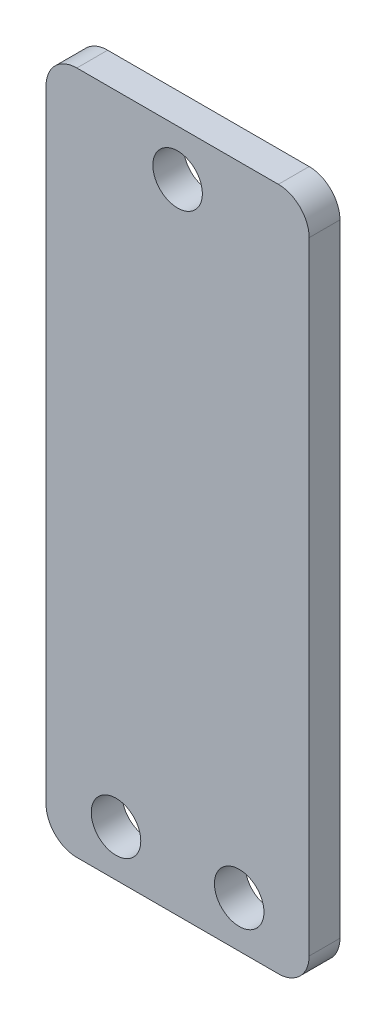
SolidWorks part; units mm, degrees
ref_plane "Front Plane" through (0, 0, 0) normal (0, 0, 1) x (1, 0, 0)
ref_plane "Top Plane" through (0, 0, 0) normal (0, 1, 0) x (1, 0, 0)
ref_plane "Right Plane" through (0, 0, 0) normal (1, 0, 0) x (0, 0, -1)
sketch "Sketch1" plane through (0, 0, 0) normal (0, 0, 1) x (1, 0, 0)
  line L0 (8.9027, -4.6609) -> (-8.9027, -4.6609) construction
  line L1 (10.3886, -4.6609) -> (-10.3886, -4.6609)
  line L2 (13.5636, -1.4859) -> (13.5636, 62.6618)
  line L3 (10.3886, 65.8368) -> (-10.3886, 65.8368)
  line L4 (-13.5636, -1.4859) -> (-13.5636, 62.6618)
  line L5 (70.917, 65.8368) -> (26.467, 65.8368) construction
  arc A0 (8.9027, -4.6609) -> (8.9027, 4.6609) centre (8.9027, 0) ccw construction
  arc A1 (-8.9027, 4.6609) -> (-8.9027, -4.6609) centre (-8.9027, 0) ccw construction
  arc A2 (13.5636, 62.6618) -> (10.3886, 65.8368) centre (10.3886, 62.6618) ccw
  arc A3 (-10.3886, 65.8368) -> (-13.5636, 62.6618) centre (-10.3886, 62.6618) ccw
  arc A4 (-10.3886, -4.6609) -> (-13.5636, -1.4859) centre (-10.3886, -1.4859) cw
  arc A5 (10.3886, -4.6609) -> (13.5636, -1.4859) centre (10.3886, -1.4859) ccw
  dimension "D1" = 3.175
extrude "Boss-Extrude1" add sketch "Sketch1" along normal blind 3.175
hole_wizard "#10 Clearance Hole1" positions "Sketch2" profile "Sketch3" hole size "#10" standard "ANSI Inch" end condition through all
sketch "Sketch2" plane through (0, 0, 3.175) normal (0, 0, 1) x (1, 0, 0)
  line L0 (6.35, 0.1016) -> (-6.35, 0.1016) construction
  line L2 (-10.3886, -4.6609) -> (10.3886, -4.6609) construction
  line L3 (10.3886, 65.8368) -> (-10.3886, 65.8368) construction
  point P0 (6.35, 0.1016)
  point P2 (-6.35, 0.1016)
  point P4 (0, 61.0743)
  point P11 (0, 0.1016)
  point P14 (0, -4.6609)
  point P18 (0, 65.8368)
  dimension "D1" = 12.7
  dimension "D2" = 4.7625
  dimension "D3" = 4.7625
sketch "Sketch3" plane through (6.35, 0.1016, 3.175) normal (1, 0, 0) x (0, -1, 0)
  line L0 (0, 0) -> (0, 3.175)
  line L1 (0, 3.175) -> (2.5527, 3.175)
  line L2 (2.5527, 3.175) -> (2.5527, 0)
  line L5 (2.5527, 0) -> (0, 0)
  line L11 (0, -6.35) -> (0, 107.95) construction
  dimension "Thru Hole Dia." = 5.1054
  dimension "Thru Hole Depth" = 3.175
